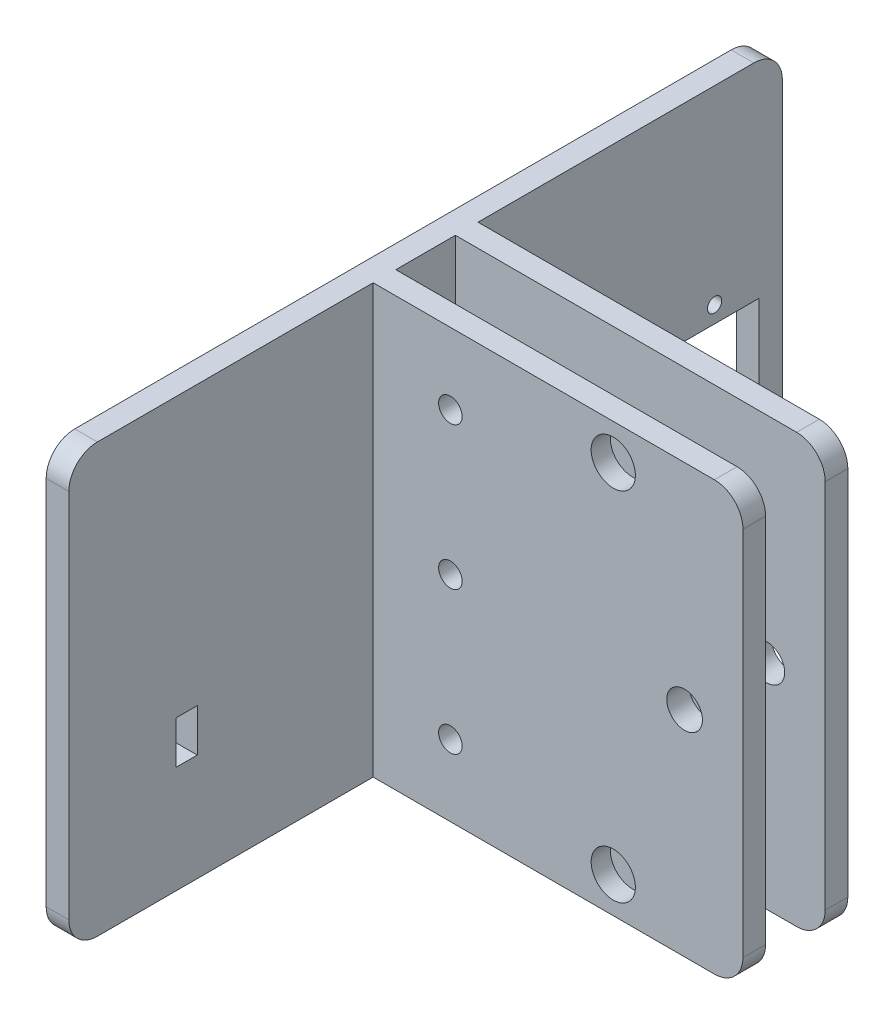
SolidWorks part; units mm, degrees
ref_plane "Front Plane" through (0, 0, 0) normal (0, 0, 1) x (1, 0, 0)
ref_plane "Top Plane" through (0, 0, 0) normal (0, 1, 0) x (1, 0, 0)
ref_plane "Right Plane" through (0, 0, 0) normal (1, 0, 0) x (0, 0, -1)
sketch "Sketch1" plane through (0, 0, 0) normal (0, 1, 0) x (1, 0, 0)
  line L0 (0, 7.35) -> (0, -7.35)
  line L5 (0, -7.35) -> (55, -7.35)
  line L6 (55, -7.35) -> (55, -4.175)
  line L17 (55, -4.175) -> (3.175, -4.175)
  line L18 (3.175, -4.175) -> (3.175, 4.175)
  line L19 (0, 0) -> (39.6882, 0) construction
  line L20 (55, 4.175) -> (3.175, 4.175)
  line L21 (55, 7.35) -> (55, 4.175)
  line L22 (0, 7.35) -> (55, 7.35)
  point P9 (3.175, 0)
  dimension "D1" = 14.7
  dimension "D2" = 3.175
  dimension "D3" = 3.175
  dimension "D4" = 55
extrude "Boss-Extrude1" add sketch "Sketch1" along normal blind 60
sketch "Sketch3" plane through (0, 0, 7.35) normal (0, 0, 1) x (1, 0, 0)
  line L1 (55, 60) -> (55, 0) construction
  line L2 (0, 60) -> (55, 60) construction
  line L3 (55, 30) -> (0, 30) construction
  line L4 (0, 60) -> (0, 0) construction
  circle A0 centre (36.825, 55) radius 3.1
  circle A2 centre (36.825, 5) radius 3.1
  dimension "D1" = 6.2
  dimension "D2" = 5
  dimension "D3" = 18.175
extrude "Cut-Extrude1" cut sketch "Sketch3" against normal blind 2.7
sketch "Sketch4" plane through (0, 0, -7.35) normal (0, 0, -1) x (-1, 0, 0)
  line L1 (-55, 60) -> (-55, 0) construction
  line L2 (0, 60) -> (-55, 60) construction
  line L3 (-55, 30) -> (0, 30) construction
  line L4 (0, 60) -> (0, 0) construction
  circle A0 centre (-36.825, 55) radius 3.1
  circle A2 centre (-36.825, 5) radius 3.1
  dimension "D4" = 6.2
  dimension "D1" = 5
  dimension "D2" = 18.175
extrude "Cut-Extrude2" cut sketch "Sketch4" against normal blind 2.7
fillet "Fillet1" radius 4 4 edges at (55, 60, 5.7625) (55, 60, -5.7625) (55, 0, -5.7625) (55, 0, 5.7625)
sketch "Sketch5" plane through (0, 0, 7.35) normal (0, 0, 1) x (1, 0, 0)
  line L0 (0, 30) -> (55, 30) construction
  line L1 (0, 60) -> (0, 0) construction
  line L2 (55, 56) -> (55, 4) construction
  circle A0 centre (14, 10) radius 1.65
  circle A1 centre (14, 50) radius 1.65
  circle A2 centre (14, 30) radius 1.65
  point P10 (0, 0)
  dimension "D3" = 3.3
  dimension "D1" = 20
  dimension "D2" = 20
  dimension "D4" = 14
extrude "Cut-Extrude3" cut sketch "Sketch5" against normal up to surface (14.7 mm away) up to face at (33.725, 55, -7.35)
sketch "Sketch6" plane through (0, 0, 7.35) normal (0, 0, 1) x (1, 0, 0)
  line L0 (0, 0) -> (51, 0) construction
  line L1 (0, 60) -> (3.175, 60)
  line L2 (0, 60) -> (0, 0)
  line L3 (0, 0) -> (3.175, 0)
  line L4 (3.175, 60) -> (3.175, 0)
  dimension "D1" = 3.175
extrude "Boss-Extrude2" add sketch "Sketch6" along normal blind 42.65
sketch "Sketch7" plane through (0, 0, -7.35) normal (0, 0, -1) x (-1, 0, 0)
  line L0 (-51, 60) -> (0, 60) construction
  line L1 (0, 0) -> (-3.175, 0)
  line L2 (0, 0) -> (0, 60)
  line L3 (0, 60) -> (-3.175, 60)
  line L4 (-3.175, 0) -> (-3.175, 60)
  dimension "D1" = 3.175
extrude "Boss-Extrude3" add sketch "Sketch7" along normal blind 42.65
fillet "Fillet2" radius 4 4 edges at (1.5875, 0, -50) (1.5875, 60, -50) (1.5875, 0, 50) (1.5875, 60, 50)
sketch "Sketch10" plane through (0, 0, 0) normal (-1, 0, 0) x (0, 0, 1)
  line L0 (-50, 4) -> (-50, 56) construction
  line L3 (-46, 0) -> (46, 0) construction
  line L5 (-34.25, 31.075) -> (-46.75, 31.075)
  line L6 (-34.25, 31.075) -> (-34.25, 8.325)
  line L7 (-34.25, 8.325) -> (-46.75, 8.325)
  line L8 (-46.75, 31.075) -> (-46.75, 8.325)
  circle A0 centre (-40.5, 6) radius 1
  circle A1 centre (-40.5, 33.4) radius 1
  dimension "D1" = 2
  dimension "D2" = 27.4
  dimension "D3" = 9.5
  dimension "D4" = 6
  dimension "D5" = 12.5
  dimension "D6" = 22.75
  dimension "D7" = 2.325
  dimension "D8" = 6.25
extrude "Cut-Extrude7" cut sketch "Sketch10" against normal up to surface (3.175 mm away) up to face at (3.175, 30, -34.7261)
sketch "Sketch11" plane through (0, 0, 0) normal (-1, 0, 0) x (0, 0, 1)
  line L0 (-50, 30) -> (50, 30) construction
  line L1 (-50, 4) -> (-50, 56) construction
  line L2 (50, 56) -> (50, 4) construction
  line L3 (-46, 0) -> (46, 0) construction
  circle A0 centre (-30, 5) radius 3.05
  circle A1 centre (-30, 55) radius 3.05
  dimension "D3" = 6.1
  dimension "D1" = 5
  dimension "D2" = 20
extrude "Cut-Extrude8" cut sketch "Sketch11" against normal blind 2.7
sketch "Sketch12" plane through (3.175, 0, 0) normal (1, 0, 0) x (0, 0, -1)
  line L0 (-46, 0) -> (-7.35, 0) construction
  line L1 (-35, 15) -> (-32, 15)
  line L2 (-35, 15) -> (-35, 21)
  line L3 (-35, 21) -> (-32, 21)
  line L4 (-32, 15) -> (-32, 21)
  line L5 (-50, 4) -> (-50, 56) construction
  line L6 (46, 0) -> (7.35, 0) construction
  line L7 (26.25, 15) -> (29.25, 15)
  line L8 (26.25, 15) -> (26.25, 21)
  line L9 (26.25, 21) -> (29.25, 21)
  line L10 (29.25, 15) -> (29.25, 21)
  line L11 (34.25, 31.075) -> (34.25, 8.325) construction
  dimension "D4" = 6
  dimension "D1" = 15
  dimension "D2" = 15
  dimension "D3" = 3
  dimension "D5" = 15
  dimension "D6" = 6
  dimension "D7" = 3
  dimension "D8" = 5
extrude "Cut-Extrude9" cut sketch "Sketch12" against normal up to surface (3.175 mm away) up to face at (0, 5, -26.95)
sketch "Sketch13" plane through (0, 0, 7.35) normal (0, 0, 1) x (1, 0, 0)
  line L0 (55, 56) -> (55, 4) construction
  line L1 (3.175, 0) -> (51, 0) construction
  circle A0 centre (46.82, 30) radius 2.5
  point P4 (0, 0)
  dimension "D3" = 5
  dimension "D1" = 8.18
  dimension "D2" = 30
extrude "Cut-Extrude10" cut sketch "Sketch13" against normal up to surface (14.7 mm away) up to face at (39.925, 5, -7.35)
equation "\"D2@Sketch5\"=\"D1@Sketch5\""
equation "\"D7@Sketch10\"=(\"D2@Sketch10\"-\"D6@Sketch10\")/2"
equation "\"D8@Sketch10\"=\"D5@Sketch10\"/2"
equation "\"D5@Sketch12\"=\"D1@Sketch12\""
equation "\"D6@Sketch12\"=\"D4@Sketch12\""
equation "\"D7@Sketch12\"=\"D3@Sketch12\""
